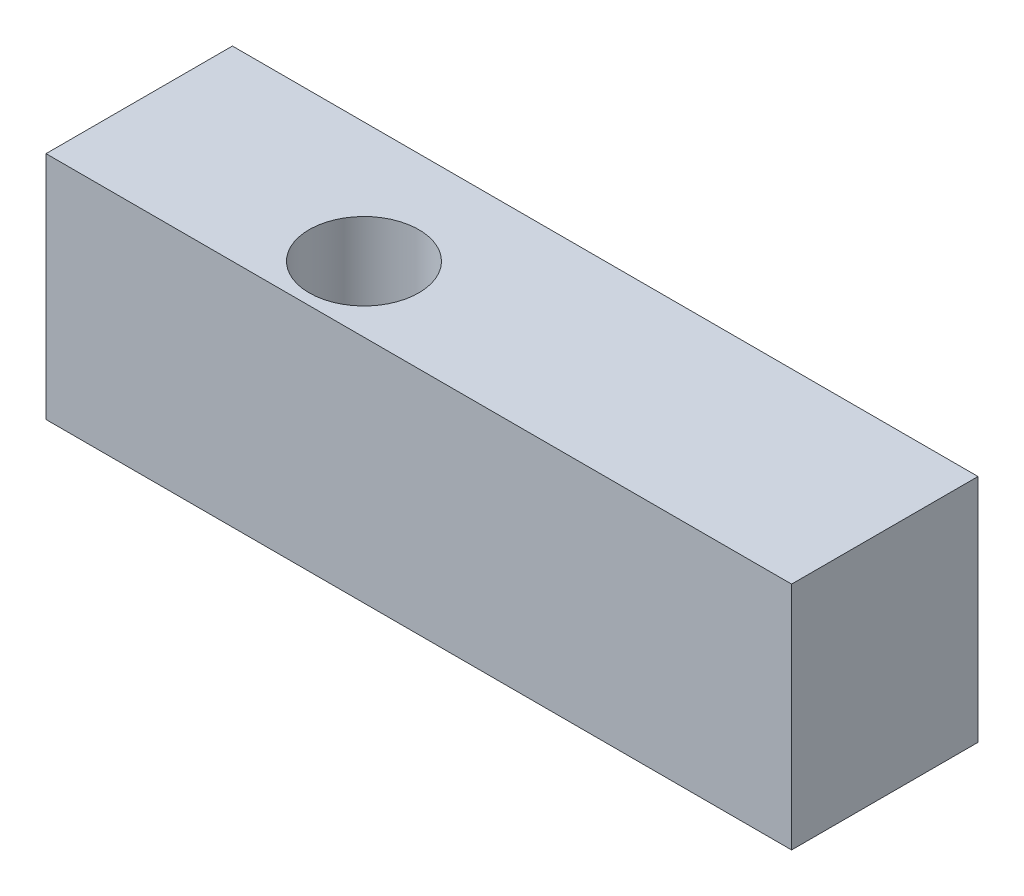
SolidWorks part; units mm, degrees
ref_plane "Front Plane" through (0, 0, 0) normal (0, 0, 1) x (1, 0, 0)
ref_plane "Top Plane" through (0, 0, 0) normal (0, 1, 0) x (1, 0, 0)
ref_plane "Right Plane" through (0, 0, 0) normal (1, 0, 0) x (0, 0, -1)
sketch "Sketch1" plane through (0, 0, 0) normal (0, 0, 1) x (1, 0, 0)
  line L1 (-4.7947, 2.3825) -> (12.4773, 2.3825)
  line L2 (-4.7947, 2.3825) -> (-4.7947, -2.9515)
  line L3 (-4.7947, -2.9515) -> (12.4773, -2.9515)
  line L4 (12.4773, 2.3825) -> (12.4773, -2.9515)
  dimension "D1" = 5.334
  dimension "D2" = 17.272
extrude "Boss-Extrude1" add sketch "Sketch1" along normal blind 4.318
sketch "Sketch2" plane through (0, 2.3825, 0) normal (0, 1, 0) x (1, 0, 0)
  line L1 (-4.7947, -4.318) -> (-4.7947, 0) construction
  line L2 (12.4773, 0) -> (-4.7947, 0) construction
  circle A0 centre (1.0473, -2.794) radius 1.27
  dimension "D1" = 2.794
  dimension "D2" = 5.842
extrude "Cut-Extrude2" cut sketch "Sketch2" against normal through all
equation "\"MDF\"= .21in"
equation "\"Foamcore\"= .13in"
equation "\"Gmaterial\"= \"MDF\""
equation "\"D1@Sketch1\"=\"MDF\""
